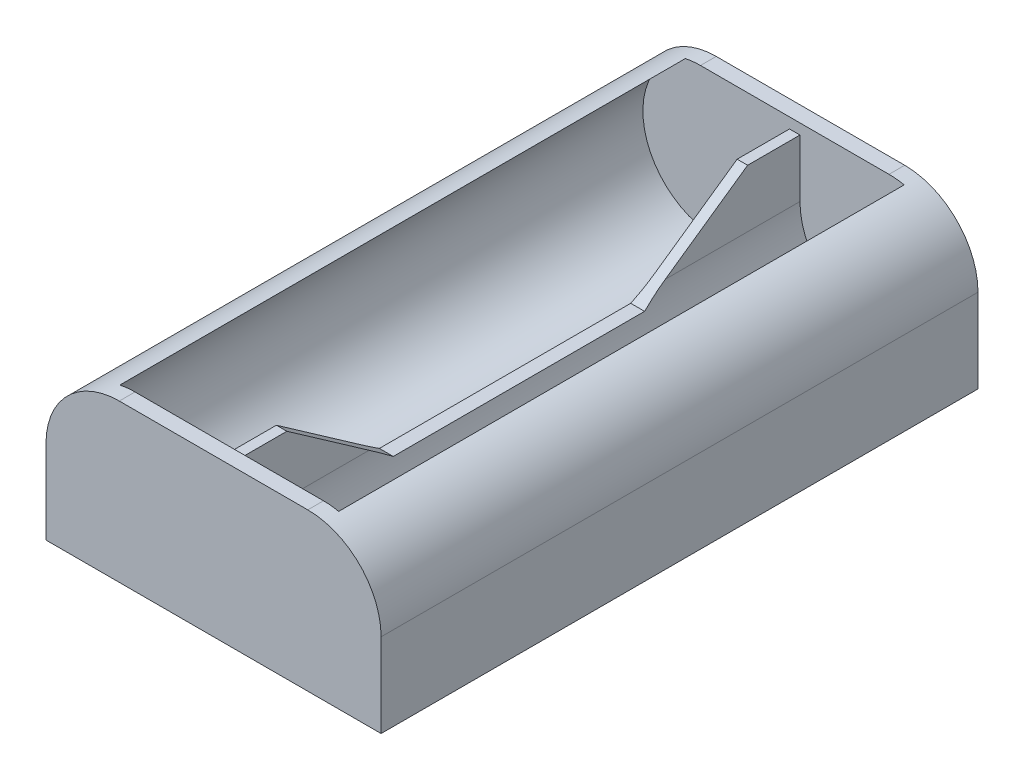
SolidWorks part; units mm, degrees
material "PF"
ref_plane "Front Plane" through (0, 0, 0) normal (0, 0, 1) x (1, 0, 0)
ref_plane "Top Plane" through (0, 0, 0) normal (0, 1, 0) x (1, 0, 0)
ref_plane "Right Plane" through (0, 0, 0) normal (1, 0, 0) x (0, 0, -1)
sketch "Sketch1" plane through (0, 0, 0) normal (0, 1, 0) x (1, 0, 0)
  line L0 (0, 0) -> (0, -55.5)
  line L2 (47, -55.5) -> (47, 0)
  line L3 (47, 0) -> (0, 0)
  line L5 (0, -55.5) -> (47, -55.5)
extrude "Boss-Extrude1" add sketch "Sketch1" along normal blind 15
sketch "Sketch2" plane through (0, 0, 55.5) normal (0, 0, 1) x (1, 0, 0)
  line L0 (0, 15) -> (47, 15) construction
  line L1 (0, 15) -> (47, 15)
  line L2 (0, 15) -> (0, 0)
  line L3 (0, 0) -> (47, 0)
  line L4 (47, 15) -> (47, 0)
  line L5 (0, 15) -> (0, 0) construction
  circle A0 centre (8.5, 8.5) radius 7
  circle A1 centre (23.5, 8.5) radius 7
  circle A2 centre (38.5, 8.5) radius 7
extrude "Cut-Extrude4" cut sketch "Sketch2" against normal blind 54 contours L1 A0 | L1 A1 | L1 A2 region at (8.5, 8.4232, 55.5) region at (23.5, 8.4232, 55.5) region at (38.5, 8.4232, 55.5)
fillet "Fillet1" radius 7 1 edges at (47, 15, 27.75) type face fillet first side face at (23.5, 15, 28.3125) second side face at (47, 7.5, 27.75)
fillet "Fillet2" radius 7 1 edges at (0, 15, 27.75) type face fillet first side face at (19.986, 15, 24.4286) second side face at (0, 7.5, 27.75)
sketch "Sketch3" plane through (0, 0, 55.5) normal (0, 0, 1) x (1, 0, 0)
  line L0 (30.5, 8.5) -> (30.5, 15)
  line L1 (26.0981, 15) -> (35.9019, 15) construction
  line L3 (26.0981, 15) -> (26.0981, 8.5)
  line L4 (26.0981, 8.5) -> (30.5, 8.5)
  line L5 (35.9019, 8.5) -> (35.9019, 15)
  line L6 (35.9019, 15) -> (31.5, 15)
  line L7 (31.5, 8.5) -> (31.5, 15)
  line L8 (30.5, 15) -> (26.0981, 15)
  line L9 (31.5, 8.5) -> (35.9019, 8.5)
  line L11 (15.5, 8.5) -> (11.0981, 8.5)
  line L12 (16.5, 15) -> (20.9019, 15)
  line L13 (15.5, 8.5) -> (15.5, 15)
  line L14 (11.0981, 15) -> (15.5, 15)
  line L15 (11.0981, 8.5) -> (11.0981, 15)
  line L16 (20.9019, 8.5) -> (16.5, 8.5)
  line L17 (20.9019, 15) -> (20.9019, 8.5)
  line L18 (16.5, 8.5) -> (16.5, 15)
  arc A1 (20.9019, 15) -> (26.0981, 15) centre (23.5, 8.5) ccw construction
  arc A2 (35.9019, 15) -> (41.4494, 14.8483) centre (38.5, 8.5) ccw construction
extrude "Cut-Extrude5" cut sketch "Sketch3" against normal blind 54
sketch "Sketch4" plane through (0, 0, 55.5) normal (0, 0, 1) x (1, 0, 0)
  line L0 (15.5, 15) -> (15.5, 14)
  line L2 (15.5, 14) -> (16.5, 14)
  line L3 (16.5, 15) -> (16.5, 8.5) construction
  line L4 (16.5, 14) -> (16.5, 15)
  line L5 (16.5, 15) -> (15.5, 15)
  line L6 (16.5, 15) -> (30.5, 15) construction
  line L7 (23.5, 15) -> (23.5, 12.7021)
  line L8 (30.5, 14) -> (30.5, 15)
  line L9 (31.5, 14) -> (30.5, 14)
  line L10 (31.5, 15) -> (31.5, 14)
  line L11 (30.5, 15) -> (31.5, 15)
  line M7 (16.5, 15) -> (15.5, 15)
  line M8 (15.5, 15) -> (15.5, 8.5)
  line M16 (31.5, 8.5) -> (31.5, 15)
  line M17 (31.5, 15) -> (30.5, 15)
  line M18 (30.5, 15) -> (30.5, 8.5)
  line M20 (16.5, 8.5) -> (16.5, 15)
extrude "Cut-Extrude6" cut sketch "Sketch4" against normal blind 54 contours L2 M8 M20 M7 | L9 M16 M17 M18 region at (16, 14.5, 55.5) region at (31, 14.5, 55.5)
sketch "Sketch5" plane through (15.5, 0, 0) normal (-1, 0, 0) x (0, 0, 1)
  line L0 (6.5, 14) -> (50.5, 14)
  line L1 (1.5, 14) -> (55.5, 14) construction
  line L4 (6.5, 14) -> (16.5, 7)
  line L5 (28.5, 14) -> (28.5, 8.5) construction
  line L6 (1.5, 8.5) -> (55.5, 8.5) construction
  line L9 (50.5, 14) -> (40.5, 7)
  line L10 (40.5, 7) -> (16.5, 7)
extrude "Cut-Extrude7" cut sketch "Sketch5" against normal blind 20
extrude "Cut-Extrude8" cut sketch "Sketch5<2>" along normal blind 5
sketch "Sketch5<2>" plane through (15.5, 0, 0) normal (-1, 0, 0) x (0, 0, 1) same geometry as "Sketch5"
sketch "Sketch6" plane through (0, 0, 55.5) normal (0, 0, 1) x (1, 0, 0)
  line L0 (0, 0) -> (47, 0)
  line L1 (47, 0) -> (47, 8)
  line L2 (40, 15) -> (7, 15)
  line L3 (0, 8) -> (0, 0)
  arc A0 (47, 8) -> (40, 15) centre (40, 8) ccw
  arc A2 (7, 15) -> (0, 8) centre (7, 8) ccw
extrude "Boss-Extrude3" add sketch "Sketch6" along normal blind 1.5
sketch "Sketch7" plane through (0, 0, 57) normal (0, 0, 1) x (1, 0, 0)
  line L1 (16, 8) -> (16, 15)
  line L2 (40, 15) -> (7, 15) construction
  line L3 (16, 8) -> (16, 0)
  line L4 (0, 0) -> (47, 0) construction
  line L5 (16, 0) -> (47, 0)
  line L6 (47, 0) -> (47, 15)
  line L7 (47, 15) -> (16, 15)
extrude "Cut-Extrude9" cut sketch "Sketch7" against normal blind 57
mirror "Mirror1" about plane through (16, 8, 0) normal (-1, 0, 0) of bodies 112
